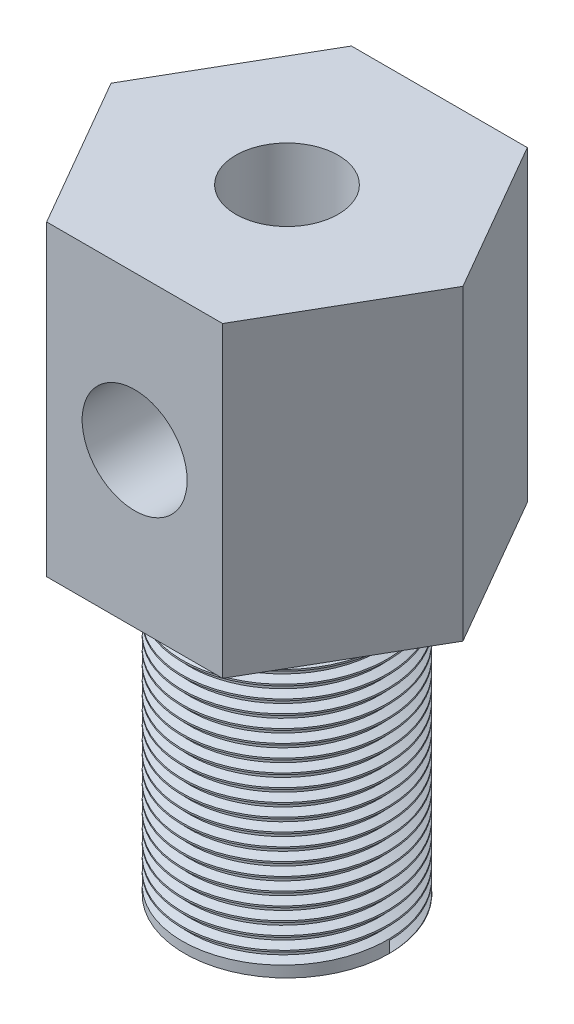
SolidWorks part; units mm, degrees
ref_plane "Спереди" through (0, 0, 0) normal (0, 0, 1) x (1, 0, 0)
ref_plane "Сверху" through (0, 0, 0) normal (0, 1, 0) x (1, 0, 0)
ref_plane "Справа" through (0, 0, 0) normal (1, 0, 0) x (0, 0, -1)
sketch "Эскиз1" plane through (0, 0, 0) normal (0, 1, 0) x (1, 0, 0)
  line L1 (3.4352, 0) -> (1.7176, 2.975)
  line L2 (1.7176, 2.975) -> (-1.7176, 2.975)
  line L3 (-1.7176, 2.975) -> (-3.4352, 0)
  line L4 (-3.4352, 0) -> (-1.7176, -2.975)
  line L5 (-1.7176, -2.975) -> (1.7176, -2.975)
  line L6 (1.7176, -2.975) -> (3.4352, 0)
  circle A0 centre (0, 0) radius 2.975 construction
  dimension "D1" = 5.95
extrude "База" add sketch "Эскиз1" along normal blind 6
sketch "Эскиз2" plane through (0, 0, 0) normal (0, -1, 0) x (1, 0, 0)
  circle A0 centre (0, 0) radius 2
  dimension "D1" = 4
extrude "Винт" add sketch "Эскиз2" along normal blind 6
sketch "Эскиз3" plane through (0, 6, 0) normal (0, 1, 0) x (1, 0, 0)
  circle A0 centre (0, 0) radius 1
  dimension "D1" = 2
extrude "Вырез" cut sketch "Эскиз3" against normal up to surface (6 mm away) up to face at (0, 0, -2)
hole_wizard "Зажим-М2,5" positions "Эскиз6" profile "Эскиз5" tap size "M2.5" standard "DIN" end condition through all
sketch "Эскиз6" plane through (0, 0, 2.975) normal (0, 0, 1) x (1, 0, 0)
  line L1 (0, 0) -> (0, 3) construction
  line L2 (0, 3) -> (0, 6) construction
  line L3 (-1.7176, 6) -> (1.7176, 6) construction
  point P0 (0, 3)
cosmetic thread "Отверстие резьбы1" parameters "D2"=2.5
sketch "Эскиз5" plane through (0, 3, 2.975) normal (1, 0, 0) x (0, -1, 0)
  line L0 (0, 0) -> (0, 5.95)
  line L1 (0, 5.95) -> (1.025, 5.95)
  line L2 (1.025, 5.95) -> (1.025, 0)
  line L5 (1.025, 0) -> (0, 0)
  line L11 (0, -6.35) -> (0, 107.95) construction
  dimension "Диаметр проходного сверла" = 2.05
  dimension "Глубина проходного сверла" = 5.95
thread "Резьба1" pitch 0.25 method cut profile "Профиль резьбы1" start angle 0, offset 0, length 5.5, pitch 0.25, diameter 4
ref_plane "Плоскость1" through (2, -6, 0) normal (0, 0, 1) x (1, 0, 0)
sketch "Профиль резьбы1" plane through (2, -6, 0) normal (0, 0, 1) x (1, 0, 0)
  line L0 (0, 0) -> (0, 0.25) construction
  line L11 (0, 0) -> (0, 0.2187)
  line L12 (0, 0.2187) -> (-0.1353, 0.1406)
  line L13 (-0.1353, 0.1406) -> (-0.1353, 0.0781)
  line L15 (-0.1353, 0.0781) -> (0, 0)
  line L17 (-0.1353, 0.1094) -> (0, 0.1094) construction
  point P2 (0, 0)
  dimension "Pitch" = 0.25
  dimension "Profile_Angle" = 60
  dimension "Profile_Land" = 0.0625
  dimension "Profile_Height" = 0.1353
